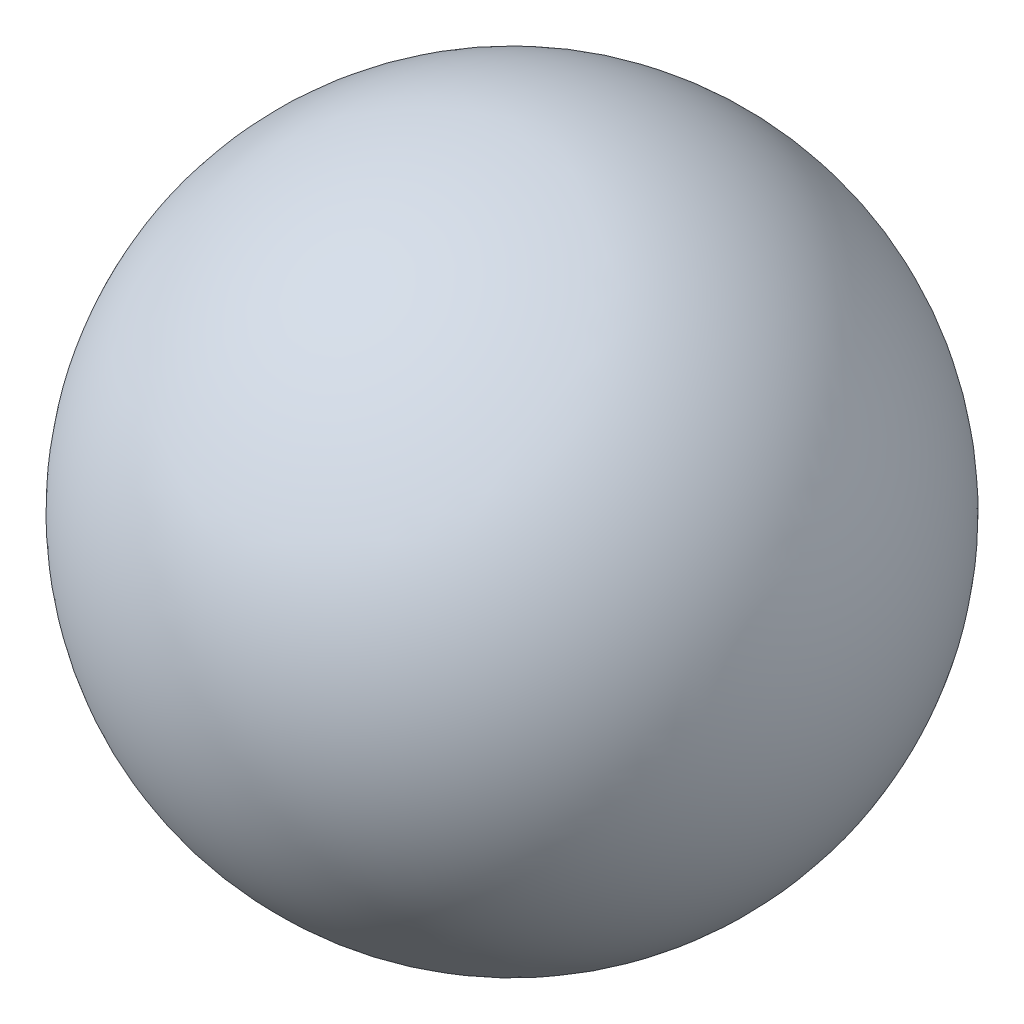
SolidWorks part; units mm, degrees
ref_plane "Front" through (0, 0, 0) normal (0, 0, 1) x (1, 0, 0)
ref_plane "Top" through (0, 0, 0) normal (0, 1, 0) x (1, 0, 0)
ref_plane "Right" through (0, 0, 0) normal (1, 0, 0) x (0, 0, -1)
sketch "Sketch2" plane through (0, 0, 0) normal (0, 1, 0) x (1, 0, 0)
  line L0 (-38.1, 0) -> (38.1, 0)
  arc A1 (-38.1, 0) -> (38.1, 0) centre (0, 0) cw
  dimension "D1" = 76.2
revolve "Revolve1" add sketch "Sketch2" angle 360 about L0
ref_plane "Plane1" through (0, 0, 0) normal (0, 1, 0) x (1, 0, 0)
ref_plane "Plane2" through (0, 0, 0) normal (0, 0, 1) x (1, 0, 0)
ref_axis "Axis1" through (-80.9, 0, 0) along (1, 0, 0)
